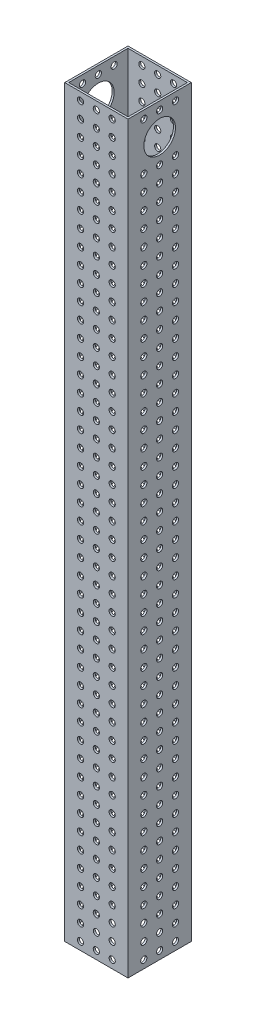
SolidWorks part; units mm, degrees
ref_plane "Front Plane" through (0, 0, 0) normal (0, 0, 1) x (1, 0, 0)
ref_plane "Top Plane" through (0, 0, 0) normal (0, 1, 0) x (1, 0, 0)
ref_plane "Right Plane" through (0, 0, 0) normal (1, 0, 0) x (0, 0, -1)
sketch "Sketch1" plane through (0, 0, 0) normal (0, 1, 0) x (1, 0, 0)
  line L1 (-25.4, 25.4) -> (25.4, 25.4)
  line L2 (-25.4, 25.4) -> (-25.4, -25.4)
  line L3 (-25.4, -25.4) -> (25.4, -25.4)
  line L4 (25.4, 25.4) -> (25.4, -25.4)
  line L5 (-25.4, 25.4) -> (25.4, -25.4) construction
  line L6 (-25.4, -25.4) -> (25.4, 25.4) construction
  line L7 (23.8125, 23.8125) -> (-23.8125, 23.8125)
  line L8 (23.8125, 23.8125) -> (23.8125, -23.8125)
  line L9 (23.8125, -23.8125) -> (-23.8125, -23.8125)
  line L10 (-23.8125, 23.8125) -> (-23.8125, -23.8125)
  line L11 (23.8125, 23.8125) -> (-23.8125, -23.8125) construction
  line L12 (23.8125, -23.8125) -> (-23.8125, 23.8125) construction
  point P0 (0, 0)
  point P6 (0, 0)
  dimension "D1" = 50.8
  dimension "D2" = 50.8
  dimension "D3" = 1.5875
  dimension "D4" = 1.5875
extrude "Boss-Extrude1" add sketch "Sketch1" along normal blind 685.8
sketch "Sketch2" plane through (0, 0, 25.4) normal (0, 0, 1) x (1, 0, 0)
  line L0 (0, 685.8) -> (0, 0) construction
  line L1 (-25.4, 685.8) -> (25.4, 685.8) construction
  line L2 (-25.4, 685.8) -> (-25.4, 0) construction
  line L3 (-6.35, 685.8) -> (-6.35, 0) construction
  line L5 (-25.4, 0) -> (25.4, 0) construction
  circle A0 centre (-12.7, 679.45) radius 2.4892
  circle A1 centre (-12.7, 666.75) radius 2.4892
  circle A2 centre (-12.7, 654.05) radius 2.4892
  circle A3 centre (-12.7, 641.35) radius 2.4892
  circle A4 centre (-12.7, 628.65) radius 2.4892
  circle A5 centre (-12.7, 615.95) radius 2.4892
  circle A6 centre (-12.7, 603.25) radius 2.4892
  circle A7 centre (-12.7, 590.55) radius 2.4892
  circle A8 centre (-12.7, 577.85) radius 2.4892
  circle A9 centre (-12.7, 565.15) radius 2.4892
  circle A10 centre (-12.7, 552.45) radius 2.4892
  circle A11 centre (-12.7, 539.75) radius 2.4892
  circle A12 centre (-12.7, 527.05) radius 2.4892
  circle A13 centre (-12.7, 514.35) radius 2.4892
  circle A14 centre (-12.7, 501.65) radius 2.4892
  circle A15 centre (-12.7, 488.95) radius 2.4892
  circle A16 centre (-12.7, 476.25) radius 2.4892
  circle A17 centre (-12.7, 463.55) radius 2.4892
  circle A18 centre (-12.7, 450.85) radius 2.4892
  circle A19 centre (-12.7, 438.15) radius 2.4892
  circle A20 centre (-12.7, 425.45) radius 2.4892
  circle A21 centre (-12.7, 412.75) radius 2.4892
  circle A22 centre (-12.7, 400.05) radius 2.4892
  circle A23 centre (-12.7, 387.35) radius 2.4892
  circle A24 centre (-12.7, 374.65) radius 2.4892
  circle A25 centre (-12.7, 361.95) radius 2.4892
  circle A26 centre (-12.7, 349.25) radius 2.4892
  circle A27 centre (-12.7, 336.55) radius 2.4892
  circle A28 centre (-12.7, 323.85) radius 2.4892
  circle A29 centre (-12.7, 311.15) radius 2.4892
  circle A30 centre (-12.7, 298.45) radius 2.4892
  circle A31 centre (-12.7, 285.75) radius 2.4892
  circle A32 centre (-12.7, 273.05) radius 2.4892
  circle A33 centre (-12.7, 260.35) radius 2.4892
  circle A34 centre (-12.7, 247.65) radius 2.4892
  circle A35 centre (-12.7, 234.95) radius 2.4892
  circle A36 centre (-12.7, 222.25) radius 2.4892
  circle A37 centre (-12.7, 209.55) radius 2.4892
  circle A38 centre (-12.7, 196.85) radius 2.4892
  circle A39 centre (-12.7, 184.15) radius 2.4892
  circle A40 centre (-12.7, 171.45) radius 2.4892
  circle A41 centre (-12.7, 158.75) radius 2.4892
  circle A42 centre (-12.7, 146.05) radius 2.4892
  circle A43 centre (-12.7, 133.35) radius 2.4892
  circle A44 centre (-12.7, 120.65) radius 2.4892
  circle A45 centre (-12.7, 107.95) radius 2.4892
  circle A46 centre (-12.7, 95.25) radius 2.4892
  circle A47 centre (-12.7, 82.55) radius 2.4892
  circle A48 centre (-12.7, 69.85) radius 2.4892
  circle A49 centre (-12.7, 57.15) radius 2.4892
  circle A50 centre (-12.7, 44.45) radius 2.4892
  circle A51 centre (-12.7, 31.75) radius 2.4892
  circle A52 centre (-12.7, 19.05) radius 2.4892
  circle A53 centre (-12.7, 6.35) radius 2.4892
  circle A54 centre (12.7, 6.35) radius 2.4892
  circle A55 centre (12.7, 19.05) radius 2.4892
  circle A56 centre (12.7, 31.75) radius 2.4892
  circle A57 centre (12.7, 44.45) radius 2.4892
  circle A58 centre (12.7, 57.15) radius 2.4892
  circle A59 centre (12.7, 69.85) radius 2.4892
  circle A60 centre (12.7, 82.55) radius 2.4892
  circle A61 centre (12.7, 95.25) radius 2.4892
  circle A62 centre (12.7, 107.95) radius 2.4892
  circle A63 centre (12.7, 120.65) radius 2.4892
  circle A64 centre (12.7, 133.35) radius 2.4892
  circle A65 centre (12.7, 146.05) radius 2.4892
  circle A66 centre (12.7, 158.75) radius 2.4892
  circle A67 centre (12.7, 171.45) radius 2.4892
  circle A68 centre (12.7, 184.15) radius 2.4892
  circle A69 centre (12.7, 196.85) radius 2.4892
  circle A70 centre (12.7, 209.55) radius 2.4892
  circle A71 centre (12.7, 222.25) radius 2.4892
  circle A72 centre (12.7, 234.95) radius 2.4892
  circle A73 centre (12.7, 247.65) radius 2.4892
  circle A74 centre (12.7, 260.35) radius 2.4892
  circle A75 centre (12.7, 273.05) radius 2.4892
  circle A76 centre (12.7, 285.75) radius 2.4892
  circle A77 centre (12.7, 298.45) radius 2.4892
  circle A78 centre (12.7, 311.15) radius 2.4892
  circle A79 centre (12.7, 323.85) radius 2.4892
  circle A80 centre (12.7, 336.55) radius 2.4892
  circle A81 centre (12.7, 374.65) radius 2.4892
  circle A82 centre (12.7, 361.95) radius 2.4892
  circle A83 centre (12.7, 349.25) radius 2.4892
  circle A84 centre (12.7, 387.35) radius 2.4892
  circle A85 centre (12.7, 400.05) radius 2.4892
  circle A86 centre (12.7, 412.75) radius 2.4892
  circle A87 centre (12.7, 425.45) radius 2.4892
  circle A88 centre (12.7, 438.15) radius 2.4892
  circle A89 centre (12.7, 450.85) radius 2.4892
  circle A90 centre (12.7, 463.55) radius 2.4892
  circle A91 centre (12.7, 476.25) radius 2.4892
  circle A92 centre (12.7, 488.95) radius 2.4892
  circle A93 centre (12.7, 501.65) radius 2.4892
  circle A94 centre (12.7, 514.35) radius 2.4892
  circle A95 centre (12.7, 527.05) radius 2.4892
  circle A96 centre (12.7, 539.75) radius 2.4892
  circle A97 centre (12.7, 552.45) radius 2.4892
  circle A98 centre (12.7, 565.15) radius 2.4892
  circle A99 centre (12.7, 577.85) radius 2.4892
  circle A100 centre (12.7, 590.55) radius 2.4892
  circle A101 centre (12.7, 603.25) radius 2.4892
  circle A102 centre (12.7, 615.95) radius 2.4892
  circle A103 centre (12.7, 628.65) radius 2.4892
  circle A104 centre (12.7, 641.35) radius 2.4892
  circle A105 centre (12.7, 654.05) radius 2.4892
  circle A106 centre (12.7, 666.75) radius 2.4892
  circle A107 centre (12.7, 679.45) radius 2.4892
  circle A108 centre (0, 6.35) radius 2.4892
  circle A109 centre (0, 19.05) radius 2.4892
  circle A110 centre (0, 31.75) radius 2.4892
  circle A111 centre (0, 44.45) radius 2.4892
  circle A112 centre (0, 57.15) radius 2.4892
  circle A113 centre (0, 69.85) radius 2.4892
  circle A114 centre (0, 82.55) radius 2.4892
  circle A115 centre (0, 95.25) radius 2.4892
  circle A116 centre (0, 107.95) radius 2.4892
  circle A117 centre (0, 120.65) radius 2.4892
  circle A118 centre (0, 133.35) radius 2.4892
  circle A119 centre (0, 146.05) radius 2.4892
  circle A120 centre (0, 158.75) radius 2.4892
  circle A121 centre (0, 171.45) radius 2.4892
  circle A122 centre (0, 184.15) radius 2.4892
  circle A123 centre (0, 196.85) radius 2.4892
  circle A124 centre (0, 209.55) radius 2.4892
  circle A125 centre (0, 222.25) radius 2.4892
  circle A126 centre (0, 234.95) radius 2.4892
  circle A127 centre (0, 247.65) radius 2.4892
  circle A128 centre (0, 260.35) radius 2.4892
  circle A129 centre (0, 273.05) radius 2.4892
  circle A130 centre (0, 285.75) radius 2.4892
  circle A131 centre (0, 298.45) radius 2.4892
  circle A132 centre (0, 311.15) radius 2.4892
  circle A133 centre (0, 323.85) radius 2.4892
  circle A134 centre (0, 336.55) radius 2.4892
  circle A135 centre (0, 349.25) radius 2.4892
  circle A136 centre (0, 361.95) radius 2.4892
  circle A137 centre (0, 374.65) radius 2.4892
  circle A138 centre (0, 387.35) radius 2.4892
  circle A139 centre (0, 400.05) radius 2.4892
  circle A140 centre (0, 412.75) radius 2.4892
  circle A141 centre (0, 425.45) radius 2.4892
  circle A142 centre (0, 438.15) radius 2.4892
  circle A143 centre (0, 450.85) radius 2.4892
  circle A144 centre (0, 463.55) radius 2.4892
  circle A145 centre (0, 476.25) radius 2.4892
  circle A146 centre (0, 488.95) radius 2.4892
  circle A147 centre (0, 501.65) radius 2.4892
  circle A148 centre (0, 514.35) radius 2.4892
  circle A149 centre (0, 527.05) radius 2.4892
  circle A150 centre (0, 539.75) radius 2.4892
  circle A151 centre (0, 552.45) radius 2.4892
  circle A152 centre (0, 565.15) radius 2.4892
  circle A153 centre (0, 577.85) radius 2.4892
  circle A154 centre (0, 590.55) radius 2.4892
  circle A155 centre (0, 603.25) radius 2.4892
  circle A156 centre (0, 615.95) radius 2.4892
  circle A157 centre (0, 628.65) radius 2.4892
  circle A158 centre (0, 641.35) radius 2.4892
  circle A159 centre (0, 654.05) radius 2.4892
  circle A160 centre (0, 666.75) radius 2.4892
  circle A161 centre (0, 679.45) radius 2.4892
  dimension "D1" = 4.9784
  dimension "D2" = 6.35
  dimension "D3" = 12.7
  dimension "D5" = 12.7
  dimension "D6" = 6.35
  dimension "D4" = 54
extrude "Cut-Extrude1" cut sketch "Sketch2" against normal through all
sketch "Sketch4" plane through (25.4, 0, 0) normal (1, 0, 0) x (0, 0, -1)
  line L0 (0, 685.8) -> (0, 0) construction
  line L1 (-25.4, 685.8) -> (25.4, 685.8) construction
  line L2 (-25.4, 685.8) -> (-25.4, 0) construction
  line L3 (-6.35, -314.2) -> (-6.35, 49685.8) construction
  line L4 (25.4, 584.2) -> (-25.4, 584.2) construction
  line L5 (25.4, 685.8) -> (25.4, 0) construction
  circle A0 centre (-12.7, 679.45) radius 2.4892
  circle A1 centre (-12.7, 666.75) radius 2.4892
  circle A2 centre (-12.7, 654.05) radius 2.4892
  circle A3 centre (-12.7, 641.35) radius 2.4892
  circle A4 centre (-12.7, 628.65) radius 2.4892
  circle A5 centre (-12.7, 615.95) radius 2.4892
  circle A6 centre (-12.7, 603.25) radius 2.4892
  circle A7 centre (-12.7, 590.55) radius 2.4892
  circle A10 centre (-12.7, 552.45) radius 2.4892
  circle A11 centre (-12.7, 539.75) radius 2.4892
  circle A12 centre (-12.7, 527.05) radius 2.4892
  circle A13 centre (-12.7, 514.35) radius 2.4892
  circle A14 centre (-12.7, 501.65) radius 2.4892
  circle A15 centre (-12.7, 488.95) radius 2.4892
  circle A16 centre (-12.7, 476.25) radius 2.4892
  circle A17 centre (-12.7, 463.55) radius 2.4892
  circle A18 centre (-12.7, 450.85) radius 2.4892
  circle A19 centre (-12.7, 438.15) radius 2.4892
  circle A20 centre (-12.7, 425.45) radius 2.4892
  circle A21 centre (-12.7, 412.75) radius 2.4892
  circle A22 centre (-12.7, 400.05) radius 2.4892
  circle A23 centre (-12.7, 387.35) radius 2.4892
  circle A24 centre (-12.7, 374.65) radius 2.4892
  circle A25 centre (-12.7, 361.95) radius 2.4892
  circle A26 centre (-12.7, 349.25) radius 2.4892
  circle A27 centre (-12.7, 336.55) radius 2.4892
  circle A28 centre (-12.7, 323.85) radius 2.4892
  circle A29 centre (-12.7, 311.15) radius 2.4892
  circle A30 centre (-12.7, 298.45) radius 2.4892
  circle A31 centre (-12.7, 285.75) radius 2.4892
  circle A32 centre (-12.7, 273.05) radius 2.4892
  circle A33 centre (-12.7, 260.35) radius 2.4892
  circle A34 centre (-12.7, 247.65) radius 2.4892
  circle A35 centre (-12.7, 234.95) radius 2.4892
  circle A36 centre (-12.7, 222.25) radius 2.4892
  circle A37 centre (-12.7, 209.55) radius 2.4892
  circle A38 centre (-12.7, 196.85) radius 2.4892
  circle A39 centre (-12.7, 184.15) radius 2.4892
  circle A40 centre (-12.7, 171.45) radius 2.4892
  circle A41 centre (-12.7, 158.75) radius 2.4892
  circle A42 centre (-12.7, 146.05) radius 2.4892
  circle A43 centre (-12.7, 133.35) radius 2.4892
  circle A44 centre (-12.7, 120.65) radius 2.4892
  circle A45 centre (-12.7, 107.95) radius 2.4892
  circle A46 centre (-12.7, 95.25) radius 2.4892
  circle A47 centre (-12.7, 82.55) radius 2.4892
  circle A48 centre (-12.7, 69.85) radius 2.4892
  circle A49 centre (-12.7, 57.15) radius 2.4892
  circle A50 centre (-12.7, 44.45) radius 2.4892
  circle A51 centre (-12.7, 31.75) radius 2.4892
  circle A52 centre (-12.7, 19.05) radius 2.4892
  circle A53 centre (-12.7, 6.35) radius 2.4892
  circle A54 centre (12.7, 273.05) radius 2.4892
  circle A55 centre (12.7, 285.75) radius 2.4892
  circle A56 centre (12.7, 298.45) radius 2.4892
  circle A57 centre (12.7, 311.15) radius 2.4892
  circle A58 centre (12.7, 323.85) radius 2.4892
  circle A59 centre (12.7, 336.55) radius 2.4892
  circle A60 centre (12.7, 349.25) radius 2.4892
  circle A61 centre (12.7, 361.95) radius 2.4892
  circle A62 centre (12.7, 374.65) radius 2.4892
  circle A63 centre (12.7, 387.35) radius 2.4892
  circle A64 centre (12.7, 400.05) radius 2.4892
  circle A65 centre (12.7, 412.75) radius 2.4892
  circle A66 centre (12.7, 425.45) radius 2.4892
  circle A67 centre (12.7, 438.15) radius 2.4892
  circle A68 centre (12.7, 450.85) radius 2.4892
  circle A69 centre (12.7, 463.55) radius 2.4892
  circle A70 centre (12.7, 476.25) radius 2.4892
  circle A71 centre (12.7, 488.95) radius 2.4892
  circle A72 centre (12.7, 501.65) radius 2.4892
  circle A73 centre (12.7, 514.35) radius 2.4892
  circle A74 centre (12.7, 527.05) radius 2.4892
  circle A75 centre (12.7, 539.75) radius 2.4892
  circle A76 centre (12.7, 552.45) radius 2.4892
  circle A79 centre (12.7, 590.55) radius 2.4892
  circle A80 centre (12.7, 603.25) radius 2.4892
  circle A81 centre (12.7, 615.95) radius 2.4892
  circle A82 centre (12.7, 628.65) radius 2.4892
  circle A83 centre (12.7, 641.35) radius 2.4892
  circle A84 centre (12.7, 654.05) radius 2.4892
  circle A85 centre (12.7, 666.75) radius 2.4892
  circle A86 centre (12.7, 19.05) radius 2.4892
  circle A87 centre (12.7, 31.75) radius 2.4892
  circle A88 centre (12.7, 44.45) radius 2.4892
  circle A89 centre (12.7, 57.15) radius 2.4892
  circle A90 centre (12.7, 69.85) radius 2.4892
  circle A91 centre (12.7, 82.55) radius 2.4892
  circle A92 centre (12.7, 95.25) radius 2.4892
  circle A93 centre (12.7, 107.95) radius 2.4892
  circle A94 centre (12.7, 120.65) radius 2.4892
  circle A95 centre (12.7, 133.35) radius 2.4892
  circle A96 centre (12.7, 146.05) radius 2.4892
  circle A97 centre (12.7, 158.75) radius 2.4892
  circle A98 centre (12.7, 171.45) radius 2.4892
  circle A99 centre (12.7, 184.15) radius 2.4892
  circle A100 centre (12.7, 196.85) radius 2.4892
  circle A101 centre (12.7, 209.55) radius 2.4892
  circle A102 centre (12.7, 222.25) radius 2.4892
  circle A103 centre (12.7, 234.95) radius 2.4892
  circle A104 centre (12.7, 247.65) radius 2.4892
  circle A105 centre (12.7, 260.35) radius 2.4892
  circle A106 centre (12.7, 6.35) radius 2.4892
  circle A107 centre (12.7, 679.45) radius 2.4892
  circle A108 centre (0, 6.35) radius 2.4892
  circle A109 centre (0, 19.05) radius 2.4892
  circle A110 centre (0, 31.75) radius 2.4892
  circle A111 centre (0, 44.45) radius 2.4892
  circle A112 centre (0, 57.15) radius 2.4892
  circle A113 centre (0, 69.85) radius 2.4892
  circle A114 centre (0, 82.55) radius 2.4892
  circle A115 centre (0, 95.25) radius 2.4892
  circle A116 centre (0, 107.95) radius 2.4892
  circle A117 centre (0, 120.65) radius 2.4892
  circle A118 centre (0, 133.35) radius 2.4892
  circle A119 centre (0, 146.05) radius 2.4892
  circle A120 centre (0, 158.75) radius 2.4892
  circle A121 centre (0, 171.45) radius 2.4892
  circle A122 centre (0, 184.15) radius 2.4892
  circle A123 centre (0, 196.85) radius 2.4892
  circle A124 centre (0, 209.55) radius 2.4892
  circle A125 centre (0, 222.25) radius 2.4892
  circle A126 centre (0, 234.95) radius 2.4892
  circle A127 centre (0, 247.65) radius 2.4892
  circle A128 centre (0, 260.35) radius 2.4892
  circle A129 centre (0, 273.05) radius 2.4892
  circle A130 centre (0, 285.75) radius 2.4892
  circle A131 centre (0, 298.45) radius 2.4892
  circle A132 centre (0, 311.15) radius 2.4892
  circle A133 centre (0, 323.85) radius 2.4892
  circle A134 centre (0, 336.55) radius 2.4892
  circle A135 centre (0, 349.25) radius 2.4892
  circle A136 centre (0, 361.95) radius 2.4892
  circle A137 centre (0, 374.65) radius 2.4892
  circle A138 centre (0, 387.35) radius 2.4892
  circle A139 centre (0, 400.05) radius 2.4892
  circle A140 centre (0, 412.75) radius 2.4892
  circle A141 centre (0, 425.45) radius 2.4892
  circle A142 centre (0, 438.15) radius 2.4892
  circle A143 centre (0, 450.85) radius 2.4892
  circle A144 centre (0, 463.55) radius 2.4892
  circle A145 centre (0, 476.25) radius 2.4892
  circle A146 centre (0, 488.95) radius 2.4892
  circle A147 centre (0, 501.65) radius 2.4892
  circle A148 centre (0, 514.35) radius 2.4892
  circle A149 centre (0, 527.05) radius 2.4892
  circle A150 centre (0, 539.75) radius 2.4892
  circle A151 centre (0, 552.45) radius 2.4892
  circle A154 centre (0, 590.55) radius 2.4892
  circle A155 centre (0, 603.25) radius 2.4892
  circle A156 centre (0, 615.95) radius 2.4892
  circle A157 centre (0, 628.65) radius 2.4892
  circle A158 centre (0, 641.35) radius 2.4892
  circle A159 centre (0, 654.05) radius 2.4892
  circle A160 centre (0, 666.75) radius 2.4892
  circle A161 centre (0, 679.45) radius 2.4892
  circle A162 centre (-12.7, 565.15) radius 2.4892 [skipped]
  circle A163 centre (-12.7, 577.85) radius 2.4892 [skipped]
  dimension "D1" = 4.9784
  dimension "D2" = 12.7
  dimension "D3" = 6.35
  dimension "D5" = 12.7
  dimension "D6" = 6.35
  dimension "D7" = 101.6
  dimension "D4" = 54
extrude "Cut-Extrude2" cut sketch "Sketch4" against normal through all
sketch "Sketch5" plane through (25.4, 0, 0) normal (1, 0, 0) x (0, 0, -1)
  line L0 (25.4, 685.8) -> (25.4, 0) construction
  line L1 (25.4, 609.6) -> (-25.4, 609.6)
  line L6 (-25.4, 685.8) -> (25.4, 685.8)
  line L7 (-25.4, 685.8) -> (-25.4, 609.6)
  line L8 (-25.4, 609.6) -> (25.4, 609.6)
  line L9 (25.4, 685.8) -> (25.4, 609.6)
  dimension "D1" = 50.8
  dimension "D2" = 76.2
  dimension "D3" = 76.2
extrude "Cut-Extrude3" cut sketch "Sketch5" against normal through all contours L9 L6 L7 L1 region at (25.4, 647.7, 0)
sketch "Sketch6" plane through (25.4, 0, 0) normal (1, 0, 0) x (0, 0, -1)
  line L0 (0, 609.6) -> (0, 0) construction
  line L1 (25.4, 609.6) -> (-25.4, 609.6) construction
  circle A0 centre (0, 571.9064) radius 12.7
  dimension "D2" = 25.4
  dimension "D1" = 37.6936
extrude "Cut-Extrude4" cut sketch "Sketch6" against normal through all
sketch "Sketch7" plane through (25.4, 0, 0) normal (1, 0, 0) x (0, 0, -1)
  line L0 (28.8601, 596.9) -> (-12.7, 596.9) construction
  line L1 (28.8601, 596.9) -> (-12.7, 596.9)
  line L2 (-12.7, 596.9) -> (-25.4, 596.9)
  line L3 (-25.4, 596.9) -> (-25.4, 609.6)
  line L4 (-25.4, 609.6) -> (25.4, 609.6)
  line L5 (25.4, 609.6) -> (25.4, 596.9)
  line L6 (-25.4, 609.6) -> (-25.4, 0) construction
  line L7 (25.4, 609.6) -> (-25.4, 609.6) construction
  point P9 (0, 0)
extrude "Cut-Extrude5" cut sketch "Sketch7" against normal through all contours L5 L4 L3 L2 L1 region at (25.4, 603.25, 0)
